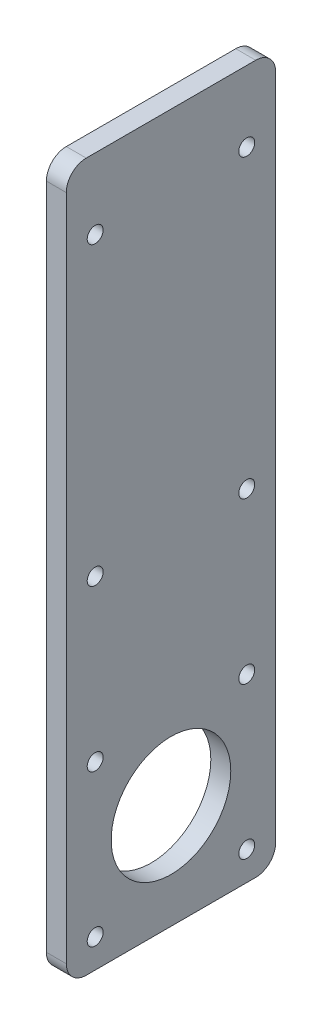
SolidWorks part; units mm, degrees
ref_plane "Front Plane" through (0, 0, 0) normal (0, 0, 1) x (1, 0, 0)
ref_plane "Top Plane" through (0, 0, 0) normal (0, 1, 0) x (1, 0, 0)
ref_plane "Right Plane" through (0, 0, 0) normal (1, 0, 0) x (0, 0, -1)
sketch "Sketch1" plane through (0, 0, 0) normal (1, 0, 0) x (0, 0, -1)
  line L0 (-15.2028, 15.2028) -> (15.2028, -15.2028) construction
  line L1 (-21, -21) -> (21, -21)
  line L2 (-21, -21) -> (-21, 21)
  line L3 (-21, 21) -> (21, 21)
  line L4 (21, -21) -> (21, 21)
  line L5 (-21, -21) -> (21, 21) construction
  line L6 (-21, 21) -> (21, -21) construction
  line L7 (-21, 21) -> (21, 21)
  line L8 (-21, 21) -> (-21, 121)
  line L9 (-21, 121) -> (21, 121)
  line L10 (21, 21) -> (21, 121)
  circle A0 centre (0, 0) radius 12
  circle A1 centre (15.2028, -15.2028) radius 1.6
  circle A2 centre (-15.2028, 15.2028) radius 1.6
  circle A3 centre (-15.2028, -15.2028) radius 1.6
  circle A4 centre (15.2028, 15.2028) radius 1.6
  point P13 (0, 0)
  dimension "D2" = 24
  dimension "D3" = 3.2
  dimension "D4" = 43
  dimension "D1" = 42
  dimension "D5" = 100
extrude "Boss-Extrude1" add sketch "Sketch1" along normal blind 4 contours L3 L10 L9 L8 | L1 L4 L3 L2 A4 A3 A2 A1 A0 region at (0, 0, 20.406) region at (0, 71, 0)
fillet "Fillet1" radius 4 4 edges at (2, -21, -21) (2, -21, 21) (2, 121, -21) (2, 121, 21)
sketch "Sketch2" plane through (4, 0, 0) normal (1, 0, 0) x (0, 0, -1)
  line L0 (15.2028, 15.2028) -> (15.2028, 47.4289) construction
  line L1 (15.2028, 47.4289) -> (-15.2028, 47.4289) construction
  line L2 (-15.2028, 15.2028) -> (-15.2028, 47.4289) construction
  line L3 (15.2028, 106.8151) -> (-15.2028, 106.8151) construction
  circle A0 centre (-15.2028, 47.4289) radius 1.6
  circle A1 centre (15.2028, 47.4289) radius 1.6
  circle A2 centre (-15.2028, 106.8151) radius 1.6
  circle A3 centre (15.2028, 106.8151) radius 1.6
  circle A4 centre (-15.2028, 15.2028) radius 1.6 construction
  point P11 (-15.2028, 105.3307)
  point P13 (0, 0)
  point P14 (15.2028, 106.8151)
extrude "Cut-Extrude1" cut sketch "Sketch2" against normal up to next
